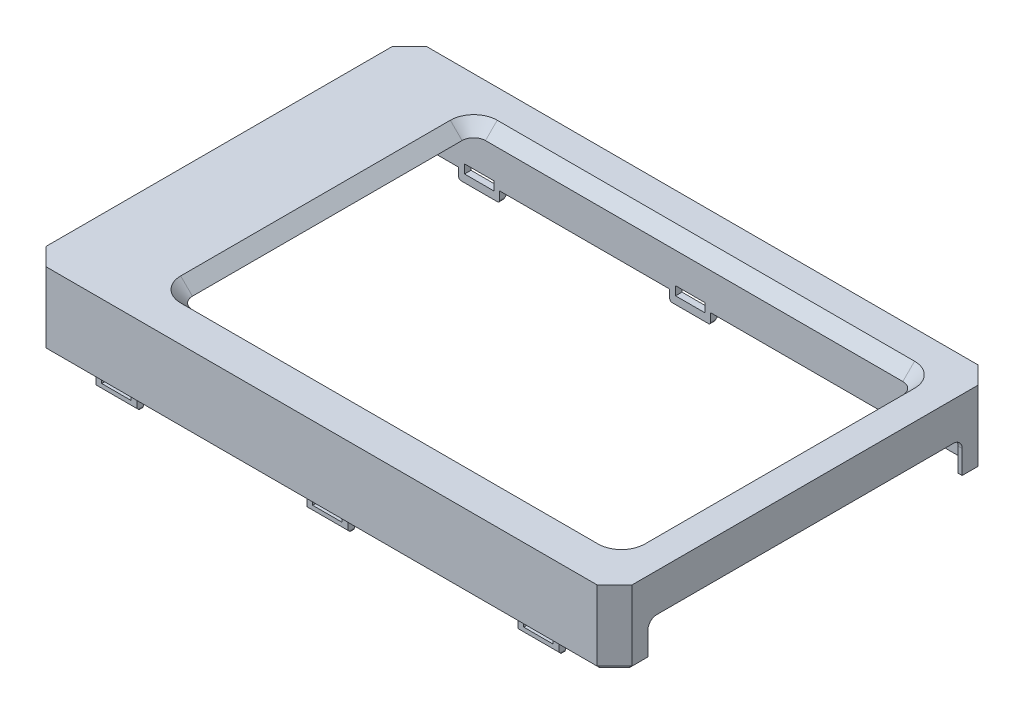
SolidWorks part; units mm, degrees
ref_plane "前视基准面" through (0, 0, 0) normal (0, 0, 1) x (1, 0, 0)
ref_plane "上视基准面" through (0, 0, 0) normal (0, 1, 0) x (1, 0, 0)
ref_plane "右视基准面" through (0, 0, 0) normal (1, 0, 0) x (0, 0, -1)
sketch "草图1" plane through (0, 0, 0) normal (0, 1, 0) x (1, 0, 0)
  line L1 (-50, 32.5) -> (50, 32.5)
  line L2 (-50, 32.5) -> (-50, -32.5)
  line L3 (-50, -32.5) -> (50, -32.5)
  line L4 (50, 32.5) -> (50, -32.5)
  line L5 (-50, 32.5) -> (50, -32.5) construction
  line L6 (-50, -32.5) -> (50, 32.5) construction
  point P0 (0, 0)
  dimension "D1" = 100
  dimension "D2" = 65
extrude "凸台-拉伸1" add sketch "草图1" along normal blind 2
sketch "草图4" plane through (0, 0, 0) normal (0, -1, 0) x (1, 0, 0)
  line L4 (-50, -32.5) -> (50, -32.5)
  line L5 (50, -32.5) -> (50, 32.5)
  line L6 (50, 32.5) -> (-50, 32.5)
  line L7 (-50, 32.5) -> (-50, -32.5)
  line L8 (-47.9, -30.4) -> (47.9, -30.4)
  line L9 (47.9, -30.4) -> (47.9, 30.4)
  line L10 (47.9, 30.4) -> (-47.9, 30.4)
  line L11 (-47.9, 30.4) -> (-47.9, -30.4)
  line L12 (-47.9, -30.4) -> (47.9, -30.4)
  line L13 (47.9, -30.4) -> (47.9, 30.4)
  line L14 (47.9, 30.4) -> (-47.9, 30.4)
  line L15 (-47.9, 30.4) -> (-47.9, -30.4)
  line L16 (-50, -32.5) -> (50, -32.5)
  line L17 (50, -32.5) -> (50, 32.5)
  line L18 (50, 32.5) -> (-50, 32.5)
  line L19 (-50, 32.5) -> (-50, -32.5)
  dimension "D1" = 2.1
  dimension "D2" = 0
extrude "凸台-拉伸2" add sketch "草图4" along normal blind 10
sketch "草图21" plane through (-50, 0, 0) normal (-1, 0, 0) x (0, 0, 1)
  line L0 (-32.5, 2) -> (32.5, 2) construction
  line L1 (-10, -2) -> (10, -2)
  line L2 (-10, -2) -> (-10, -4)
  line L3 (-10, -4) -> (10, -4)
  line L4 (10, -2) -> (10, -4)
  line L5 (-10, -2) -> (10, -4) construction
  line L6 (-10, -4) -> (10, -2) construction
  point P0 (0, -3)
  point P8 (0, 2)
  dimension "D1" = 4
  dimension "D2" = 2
  dimension "D3" = 20
chamfer "倒角4" distance 2 angle 45 4 edges at (47.9, -5, -30.4) (-47.9, -5, -30.4) (-47.9, -5, 30.4) (47.9, -5, 30.4)
chamfer "倒角5" distance 3 angle 45 4 edges at (-50, -4, -32.5) (-50, -4, 32.5) (50, -4, -32.5) (50, -4, 32.5)
sketch "草图24" plane through (47.9, 0, 0) normal (-1, 0, 0) x (0, 0, 1)
  line L0 (-28.4, -10) -> (28.4, -10) construction
  line L1 (-28.3, -10) -> (28.3, -10)
  line L2 (-28.3, -10) -> (-28.3, -4)
  line L3 (-28.3, -4) -> (28.3, -4)
  line L4 (28.3, -10) -> (28.3, -4)
  line L6 (-32.5, 2) -> (-32.5, -10) construction
  line L7 (32.5, -10) -> (32.5, 2) construction
  dimension "D1" = 4.2
  dimension "D2" = 4.2
  dimension "D3" = 6
extrude "切除-拉伸8" cut sketch "草图24" against normal blind 1.4
fillet "圆角9" radius 2 2 edges at (48.6, -4, 28.3) (48.6, -4, -28.3)
sketch "草图25" plane through (49.3, 0, 0) normal (-1, 0, 0) x (0, 0, 1)
  line L0 (-32.5, 2) -> (-32.5, -10) construction
  line L1 (32.5, -10) -> (32.5, 2) construction
  line L2 (29.5, -10) -> (-29.5, -10) construction
  line L4 (-28.3, -10) -> (28.3, -10) construction
  line L12 (26.8, -10) -> (26.8, -6)
  line L13 (25.3, -4.5) -> (-25.3, -4.5)
  line L14 (-26.8, -6) -> (-26.8, -10)
  line L15 (-26.8, -10) -> (26.8, -10)
  arc A6 (26.8, -6) -> (25.3, -4.5) centre (25.3, -6) ccw
  arc A7 (-25.3, -4.5) -> (-26.8, -6) centre (-25.3, -6) ccw
  dimension "D1" = 7.2
  dimension "D2" = 7.2
  dimension "D3" = 5.5
  dimension "D4" = 4
extrude "切除-拉伸9" cut sketch "草图25" against normal blind 11.4
sketch "草图26" plane through (0, -10, 0) normal (0, -1, 0) x (1, 0, 0)
  line L0 (45.9, 30.4) -> (47.9, 28.4)
  line L1 (-45.9, -30.4) -> (45.9, -30.4)
  line L2 (-47.9, -28.4) -> (-47.9, 28.4)
  line L3 (-45.9, 30.4) -> (45.9, 30.4)
  line L5 (-47.9, 28.4) -> (-45.9, 30.4)
  line L6 (-47.9, -28.4) -> (-45.9, -30.4)
  line L7 (45.9, -30.4) -> (47.9, -28.4)
  line L8 (-49, -28.8556) -> (-49, 28.8556)
  line L9 (-49, 28.8556) -> (-46.3556, 31.5)
  line L10 (-46.3556, 31.5) -> (46.3556, 31.5)
  line L11 (46.3556, 31.5) -> (49, 28.8556)
  line L13 (46.3556, -31.5) -> (49, -28.8556)
  line L14 (-46.3556, -31.5) -> (46.3556, -31.5)
  line L15 (-49, -28.8556) -> (-46.3556, -31.5)
  line L16 (45.9, 30.4) -> (-45.9, 30.4) construction
  line L17 (49, -28.8556) -> (49, 28.8556) construction
  line L18 (47.9, -28.4) -> (47.9, 28.4) construction
  line L19 (49, 28.8556) -> (49, 28.3)
  line L21 (49, 28.3) -> (47.9, 28.3)
  line L23 (47.9, 28.3) -> (47.9, 28.4)
  line L24 (49, -28.8556) -> (49, -28.3)
  line L26 (49, -28.3) -> (47.9, -28.3)
  line L28 (47.9, -28.3) -> (47.9, -28.4)
  line L29 (49.3, -28.3) -> (47.9, -28.3) construction
  line L30 (49.3, 28.3) -> (47.9, 28.3) construction
  point P0 (-47.9, -30.4)
  point P1 (47.9, 30.4)
  point P2 (-47.9, 30.4)
  point P3 (47.9, -30.4)
  dimension "D2" = 56.8
  dimension "D7" = 91.8
  dimension "D1" = 1.1
extrude "凸台-拉伸9" add sketch "草图26" along normal blind 1
sketch "草图30" plane through (0, 0, 0) normal (0, -1, 0) x (1, 0, 0)
  line L0 (50, 25.3) -> (50, -25.3) construction
  line L1 (45.3834, 10.75) -> (47.8, 10.75)
  line L2 (45.3834, 10.75) -> (45.3834, 9.25)
  line L3 (45.3834, 9.25) -> (47.8, 9.25)
  line L4 (47.8, 10.75) -> (47.8, 9.25)
  line L5 (45.3834, -7.25) -> (47.8, -7.25)
  line L6 (45.3834, -7.25) -> (45.3834, -8.75)
  line L7 (45.3834, -8.75) -> (47.8, -8.75)
  line L8 (47.8, -7.25) -> (47.8, -8.75)
  dimension "D1" = 2.2
  dimension "D2" = 2.4166
  dimension "D3" = 1.5
  dimension "D4" = 1.5
extrude "凸台-拉伸10" add sketch "草图30" along normal blind 6.3
chamfer "倒角8" distance 1 angle 45 2 edges at (47.8, -6.3, 10) (47.8, -6.3, -8)
sketch "草图33" plane through (-47.9, 0, 0) normal (1, 0, 0) x (0, 0, -1)
  line L1 (-7.5, -13) -> (-6, -13)
  line L2 (-7.5, -13) -> (-7.5, 0)
  line L3 (-7.5, 0) -> (-6, 0)
  line L4 (-6, -13) -> (-6, 0)
  line L6 (6, -13) -> (7.5, -13)
  line L7 (6, -13) -> (6, 0)
  line L8 (6, 0) -> (7.5, 0)
  line L9 (7.5, -13) -> (7.5, 0)
  line L10 (-32.5, -10) -> (-32.5, 2) construction
  line L11 (32.5, 2) -> (32.5, -10) construction
  line L12 (26.5, 0) -> (28, 0) construction
  line L13 (-28.4, 0) -> (28.4, 0) construction
  dimension "D1" = 25
  dimension "D2" = 25
  dimension "D3" = 13
  dimension "D4" = 1.5
extrude "凸台-拉伸11" add sketch "草图33" along normal blind 2
extrude "切除-拉伸15" cut sketch "草图21" against normal blind 5
fillet "圆角11" radius 1 4 edges at (-48.95, -2, -10) (-48.95, -4, -10) (-48.95, -2, 10) (-48.95, -4, 10)
chamfer "倒角9" distance 1 angle 45 2 edges at (-47.9, -13, 6.75) (-47.9, -13, -6.75)
sketch "草图34" plane through (0, 0, -30.4) normal (0, 0, 1) x (1, 0, 0)
  line L0 (47, -10) -> (-47, -10) construction
  line L1 (32.5, -10) -> (39.5, -10)
  line L2 (32.5, -10) -> (32.5, -12.8)
  line L3 (32.5, -12.8) -> (39.5, -12.8)
  line L4 (39.5, -10) -> (39.5, -12.8)
  line L6 (-3.5, -10) -> (3.5, -10)
  line L7 (-3.5, -10) -> (-3.5, -12.8)
  line L8 (-3.5, -12.8) -> (3.5, -12.8)
  line L9 (3.5, -10) -> (3.5, -12.8)
  line L10 (-39.5, -10) -> (-32.5, -10)
  line L11 (-39.5, -10) -> (-39.5, -12.8)
  line L12 (-39.5, -12.8) -> (-32.5, -12.8)
  line L13 (-32.5, -10) -> (-32.5, -12.8)
  dimension "D1" = 10.5
  dimension "D2" = 7
  dimension "D3" = 29
  dimension "D4" = 2.8
  dimension "D5" = 29
extrude "凸台-拉伸12" add sketch "草图34" against normal blind 1.1
sketch "草图35" plane through (0, 0, 30.4) normal (0, 0, -1) x (-1, 0, 0)
  line L4 (39.5, -10) -> (32.5, -10)
  line L5 (32.5, -10) -> (32.5, -12.8)
  line L6 (32.5, -12.8) -> (39.5, -12.8)
  line L7 (39.5, -12.8) -> (39.5, -10)
  line L8 (39.5, -10) -> (32.5, -10)
  line L9 (32.5, -10) -> (32.5, -12.8)
  line L10 (32.5, -12.8) -> (39.5, -12.8)
  line L11 (39.5, -12.8) -> (39.5, -10)
  line L12 (3.5, -10) -> (-3.5, -10)
  line L13 (-3.5, -10) -> (-3.5, -12.8)
  line L14 (-3.5, -12.8) -> (3.5, -12.8)
  line L15 (3.5, -12.8) -> (3.5, -10)
  line L16 (3.5, -10) -> (-3.5, -10)
  line L17 (-3.5, -10) -> (-3.5, -12.8)
  line L18 (-3.5, -12.8) -> (3.5, -12.8)
  line L19 (3.5, -12.8) -> (3.5, -10)
  line L20 (-32.5, -10) -> (-39.5, -10)
  line L21 (-39.5, -10) -> (-39.5, -12.8)
  line L22 (-39.5, -12.8) -> (-32.5, -12.8)
  line L23 (-32.5, -12.8) -> (-32.5, -10)
  line L24 (-32.5, -10) -> (-39.5, -10)
  line L25 (-39.5, -10) -> (-39.5, -12.8)
  line L26 (-39.5, -12.8) -> (-32.5, -12.8)
  line L27 (-32.5, -12.8) -> (-32.5, -10)
  dimension "D1" = 0
  dimension "D2" = 0
  dimension "D3" = 0
extrude "凸台-拉伸13" add sketch "草图35" against normal blind 1.1
sketch "草图36" plane through (0, 0, 31.5) normal (0, 0, 1) x (1, 0, 0)
  line L0 (46.3556, -10) -> (-46.3556, -10) construction
  line L1 (-33.5, -10) -> (-38.5, -10)
  line L2 (-33.5, -10) -> (-33.5, -11.5)
  line L3 (-33.5, -11.5) -> (-38.5, -11.5)
  line L4 (-38.5, -10) -> (-38.5, -11.5)
  line L5 (-50, -10) -> (-50, 2) construction
  line L6 (2.5, -10) -> (-2.5, -10)
  line L7 (2.5, -10) -> (2.5, -11.5)
  line L8 (2.5, -11.5) -> (-2.5, -11.5)
  line L9 (-2.5, -10) -> (-2.5, -11.5)
  line L10 (38.5, -10) -> (33.5, -10)
  line L11 (38.5, -10) -> (38.5, -11.5)
  line L12 (38.5, -11.5) -> (33.5, -11.5)
  line L13 (33.5, -10) -> (33.5, -11.5)
  dimension "D1" = 11.5
  dimension "D2" = 5
  dimension "D3" = 1.5
  dimension "D4" = 31
  dimension "D5" = 31
extrude "切除-拉伸16" cut sketch "草图36" against normal up to next
sketch "草图37" plane through (0, 0, -31.5) normal (0, 0, -1) x (-1, 0, 0)
  line L4 (-33.5, -10) -> (-38.5, -10)
  line L5 (-33.5, -11.5) -> (-33.5, -10)
  line L6 (-38.5, -11.5) -> (-33.5, -11.5)
  line L7 (-38.5, -10) -> (-38.5, -11.5)
  line L8 (-33.5, -10) -> (-38.5, -10)
  line L9 (-33.5, -11.5) -> (-33.5, -10)
  line L10 (-38.5, -11.5) -> (-33.5, -11.5)
  line L11 (-38.5, -10) -> (-38.5, -11.5)
  line L12 (2.5, -10) -> (-2.5, -10)
  line L13 (2.5, -11.5) -> (2.5, -10)
  line L14 (-2.5, -11.5) -> (2.5, -11.5)
  line L15 (-2.5, -10) -> (-2.5, -11.5)
  line L16 (2.5, -10) -> (-2.5, -10)
  line L17 (2.5, -11.5) -> (2.5, -10)
  line L18 (-2.5, -11.5) -> (2.5, -11.5)
  line L19 (-2.5, -10) -> (-2.5, -11.5)
  line L20 (38.5, -10) -> (33.5, -10)
  line L21 (38.5, -11.5) -> (38.5, -10)
  line L22 (33.5, -11.5) -> (38.5, -11.5)
  line L23 (33.5, -10) -> (33.5, -11.5)
  line L24 (38.5, -10) -> (33.5, -10)
  line L25 (38.5, -11.5) -> (38.5, -10)
  line L26 (33.5, -11.5) -> (38.5, -11.5)
  line L27 (33.5, -10) -> (33.5, -11.5)
  dimension "D1" = 0
  dimension "D2" = 0
  dimension "D3" = 0
extrude "切除-拉伸17" cut sketch "草图37" against normal up to next
chamfer "倒角11" distance 0.6 angle 45 6 edges at (36, -12.8, -31.5) (-36, -12.8, 31.5) (-36, -12.8, -31.5) (0, -12.8, -31.5) (36, -12.8, 31.5) (0, -12.8, 31.5)
fillet "圆角12" radius 0.4 12 edges at (39.5, -12.8, 30.65) (32.5, -12.8, 30.65) (-3.5, -12.8, 30.65) (3.5, -12.8, 30.65) (-32.5, -12.8, 30.65) (-39.5, -12.8, 30.65) (-39.5, -12.8, -30.65) (-32.5, -12.8, -30.65) (3.5, -12.8, -30.65) (-3.5, -12.8, -30.65) (32.5, -12.8, -30.65) (39.5, -12.8, -30.65)
sketch "草图39" plane through (0, 2, 0) normal (0, 1, 0) x (1, 0, 0)
  line L1 (-32.1526, 25.63) -> (43.0474, 25.63)
  line L2 (-32.1526, 25.63) -> (-32.1526, -24.37)
  line L3 (-32.1526, -24.37) -> (43.0474, -24.37)
  line L4 (43.0474, 25.63) -> (43.0474, -24.37)
  dimension "D1" = 75.2
  dimension "D2" = 50
extrude "切除-拉伸18" cut sketch "草图39" against normal up to next
fillet "圆角13" radius 2 4 edges at (-32.1526, 1, 24.37) (43.0474, 1, 24.37) (43.0474, 1, -25.63) (-32.1526, 1, -25.63)
chamfer "倒角12" distance 2 angle 45 8 edges at (43.0474, 2, -0.63) (42.4616, 2, -25.0442) (42.4616, 2, 23.7842) (5.4474, 2, -25.63) (5.4474, 2, 24.37) (-31.5668, 2, -25.0442) (-31.5668, 2, 23.7842) (-32.1526, 2, -0.63)
